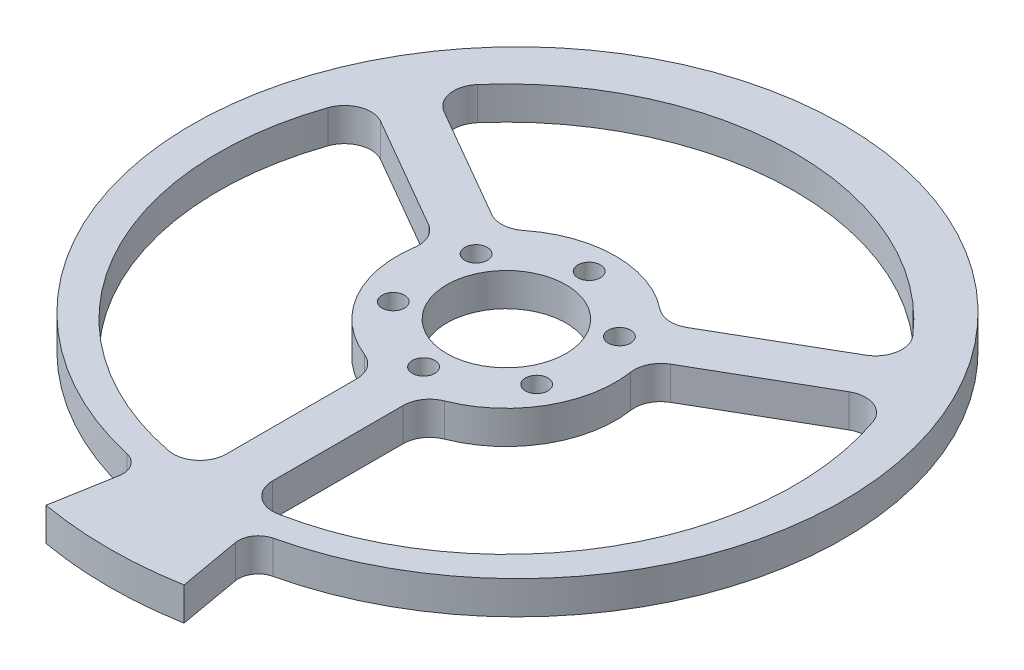
SolidWorks part; units mm, degrees
material "AISI Type A2 Tool Steel"
ref_plane "Front Plane" through (0, 0, 0) normal (0, 0, 1) x (1, 0, 0)
ref_plane "Top Plane" through (0, 0, 0) normal (0, 1, 0) x (1, 0, 0)
ref_plane "Right Plane" through (0, 0, 0) normal (1, 0, 0) x (0, 0, -1)
other "Center of Mass"
other "Bounding Box"
ref_plane "Default Plane" through (0, 2.286, 19.05) normal (0, -1, 0) x (-1, 0, 0)
sketch "Sketch1" plane through (0, 0, 0) normal (0, 1, 0) x (1, 0, 0)
  line L0 (0, -76.2) -> (0, -60.325) construction
  line L1 (0, -60.325) -> (0, -11.43) construction
  line L2 (0, -11.43) -> (0, 0) construction
  circle A0 centre (0, 0) radius 76.2 construction
  circle A1 centre (0, 0) radius 11.43
  arc A2 (0, -60.325) -> (0, 60.325) centre (0, 0) ccw
  arc A3 (0, 60.325) -> (0, -76.2) centre (0, -7.9375) ccw construction
  arc A4 (0, 60.325) -> (0, -60.325) centre (0, 0) ccw
  dimension "D1" = 152.4
  dimension "D2" = 22.86
  dimension "D3" = 120.65
extrude "Boss-Extrude2" add sketch "Sketch1" along normal mid plane 6.35
sketch "Sketch9" plane through (0, 3.175, 0) normal (0, 1, 0) x (1, 0, 0)
  line L2 (-13.232, -75.0424) -> (-10.4753, -59.4085)
  line L3 (13.232, -75.0424) -> (10.4753, -59.4085)
  line L4 (0, -76.2) -> (0, 0) construction
  circle A4 centre (0, 0) radius 60.325 construction
  arc A5 (-13.232, -75.0424) -> (13.232, -75.0424) centre (0, 0) ccw
  arc A6 (-10.4753, -59.4085) -> (10.4753, -59.4085) centre (0, 0) ccw
  dimension "D1" = 76.2
  dimension "D2" = 20
extrude "Boss-Extrude4" add sketch "Sketch9" against normal through all
sketch "Sketch6" plane through (0, 3.175, 0) normal (0, 1, 0) x (1, 0, 0)
  line L0 (-45.466, 31.3824) -> (-15.5121, 14.0886)
  line L1 (15.5121, 14.0886) -> (45.466, 31.3824)
  line L2 (0, 0) -> (-47.6885, 27.5329) construction
  line L3 (0, 0) -> (47.6885, 27.5329) construction
  line L4 (-45.466, 31.3824) -> (-47.6885, 27.5329) construction
  line L5 (45.466, 31.3824) -> (47.6885, 27.5329) construction
  line L6 (0, 0) -> (0, 60.325) construction
  arc A0 (-15.5121, 14.0886) -> (15.5121, 14.0886) centre (0, 0) cw
  arc A1 (-45.466, 31.3824) -> (45.466, 31.3824) centre (0, 0) cw
  circle A2 centre (0, 0) radius 11.43 construction
  circle A3 centre (0, 0) radius 60.325 construction
  arc A6 (10.4753, -59.4085) -> (-10.4753, -59.4085) centre (0, 0) ccw construction
  dimension "D3" = 60
  dimension "D4" = 5.08
  dimension "D1" = 9.525
  dimension "D2" = 4.445
  dimension "D5" = 60
extrude "Cut-Extrude2" cut sketch "Sketch6" against normal through all
pattern_circular "CirPattern1" count 3 over 360 about axis through (0, 3.175, 0) along (0, -1, 0) of "Cut-Extrude2"
sketch "Sketch7" [suppressed] plane through (0, 6.35, 0) normal (0, 1, 0) x (1, 0, 0)
  line L0 (12.4559, 70.0208) -> (11.1213, 62.5185)
  line L1 (70.0208, -12.4559) -> (62.5185, -11.1213)
  line L2 (0, 0) -> (52.0712, 36.3433) construction
  line L3 (0, 0) -> (0, 63.5) construction
  line L4 (-6.2364, -4.3527) -> (0, 0) construction
  arc A0 (70.0208, -12.4559) -> (12.4559, 70.0208) centre (0, 0) ccw
  arc A1 (2.4423, -63.453) -> (0, 63.5) centre (0, 0) ccw construction
  arc A2 (62.5185, -11.1213) -> (11.1213, 62.5185) centre (0, 0) ccw
  dimension "D1" = 7.62
  dimension "D3" = 90
sketch "Sketch10" plane through (0, 3.175, 0) normal (0, 1, 0) x (1, 0, 0)
  line L0 (0, 20.955) -> (0, 15.875) construction
  line L1 (0, 15.875) -> (0, 11.43) construction
  circle A0 centre (0, 15.875) radius 2.159
  circle A1 centre (0, 15.875) radius 3.9624 construction
  circle A2 centre (0, 0) radius 11.43 construction
  arc A3 (4.445, -20.4781) -> (19.9571, 6.3896) centre (0, 0) ccw construction
  dimension "D1" = 4.318
  dimension "D2" = 7.9248
  dimension "D3" = 15.875
extrude "Cut-Extrude3" cut sketch "Sketch10" against normal through all
pattern_circular "CirPattern8" count 6 over 360 about axis through (0, 3.175, 0) along (0, -1, 0) of "Cut-Extrude3" reverse direction yes
sketch "Sketch13" plane through (0, 3.175, 0) normal (0, 1, 0) x (1, 0, 0)
  line L0 (0, -60.325) -> (0, 0) construction
  line L1 (0, 60.325) -> (0, 64.5871) construction
  line L2 (-10.4753, -59.4085) -> (-10.4808, -59.4393)
  line L3 (-10.4753, -59.4085) -> (-13.232, -75.0424) construction
  line L4 (10.4753, -59.4085) -> (10.4808, -59.4393)
  line L5 (13.232, -75.0424) -> (10.4753, -59.4085) construction
  arc A2 (10.4753, -59.4085) -> (-10.4753, -59.4085) centre (0, 0) ccw construction
  arc A3 (10.4808, -59.4393) -> (-10.4808, -59.4393) centre (0, 2.1311) ccw
  arc A4 (10.4753, -59.4085) -> (-10.4753, -59.4085) centre (0, 0) ccw construction
  arc A5 (10.4753, -59.4085) -> (-10.4753, -59.4085) centre (0, 0) ccw
  arc A6 (-10.4808, -59.4393) -> (0, -60.325) centre (0, 2.1311) ccw construction
  arc A7 (0, -60.325) -> (10.4808, -59.4393) centre (0, 2.1311) ccw construction
  dimension "D1" = 4.2621
extrude "Boss-Extrude5" add sketch "Sketch13" against normal through all
fillet "Fillet2" radius 3.81 2 edges at (10.4808, 0, 59.4393) (-10.4808, 0, 59.4393)
fillet "Fillet3" radius 5.08 12 edges at (-45.466, 0, -31.3824) (45.466, 0, -31.3824) (15.5121, 0, -14.0886) (-15.5121, 0, -14.0886) (4.445, 0, 55.0659) (49.911, 0, -23.6835) (19.9571, 0, -6.3896) (4.445, 0, 20.4781) (-4.445, 0, 55.0659) (-4.445, 0, 20.4781) (-19.9571, 0, -6.3896) (-49.911, 0, -23.6835)
other "Center of Mass Reference Point2"
equation "\"Unit Measure\"= \"BoundingVolume\" / \"Thickness\"'in^2"
